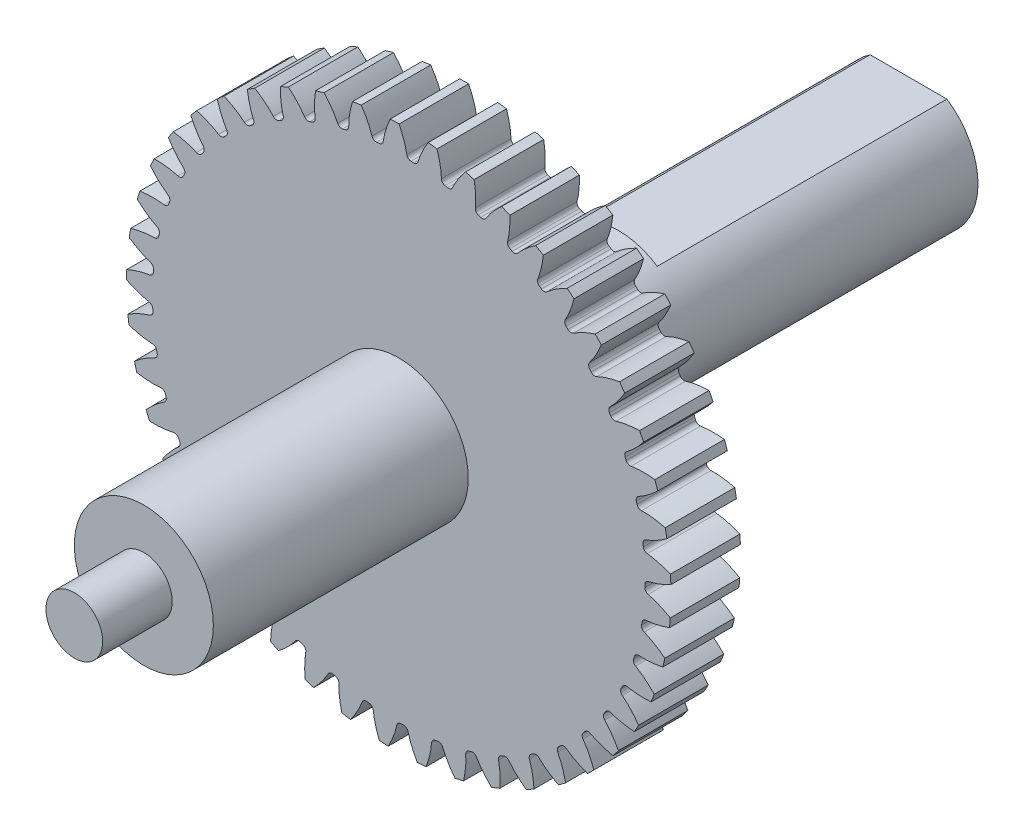
SolidWorks part; units mm, degrees
ref_plane "Front Plane" through (0, 0, 0) normal (0, 0, 1) x (1, 0, 0)
ref_plane "Top Plane" through (0, 0, 0) normal (0, 1, 0) x (1, 0, 0)
ref_plane "Right Plane" through (0, 0, 0) normal (1, 0, 0) x (0, 0, -1)
sketch "Sketch1" plane through (0, 0, 0) normal (0, 0, 1) x (1, 0, 0)
  circle A0 centre (0, 0) radius 3
  circle A1 centre (0, 0) radius 1.225
  dimension "D1" = 2.45
  dimension "D2" = 6
extrude "Boss-Extrude1" add sketch "Sketch1" along normal blind 33 contours A0
extrude "Boss-Extrude2" add sketch "Sketch1<3>" along normal blind 36 contours A1
sketch "Sketch1<3>" plane through (0, 0, 0) normal (0, 0, 1) x (1, 0, 0) same geometry as "Sketch1"
sketch "Sketch3" plane through (0, 0, 0) normal (0, 0, -1) x (-1, 0, 0)
  line L0 (-1.6583, 2.5) -> (1.6583, 2.5)
  line L1 (3.3, 0) -> (-3.3, 0) construction
  circle A0 centre (0, 0) radius 3 construction
  arc A1 (1.6583, 2.5) -> (-1.6583, 2.5) centre (0, 0) ccw
  dimension "D1" = 2.5
extrude "Cut-Extrude1" cut sketch "Sketch3" against normal blind 12.5
ref_plane "Plane1" through (0, 0, 19) normal (0, 0, 1) x (1, 0, 0)
sketch "Sketch4" plane through (0, 0, 19) normal (0, 0, 1) x (1, 0, 0)
  spline S0 degree 4 poles (10.5715, 0) (10.5764, 0.0001) (10.5899, 0.0006) (10.6154, 0.0024) (10.657, 0.0069) (10.7098, 0.0146) (10.7777, 0.0269) (10.8574, 0.0443) (10.9445, 0.0666) (11.0386, 0.0942) (11.1319, 0.1247) (11.2243, 0.1579) (11.3158, 0.1934) (11.4258, 0.2392) (11.5566, 0.2981) (11.7078, 0.3727) (11.8769, 0.4641) (12.0467, 0.5643) (12.2115, 0.6686) (12.3753, 0.7806) (12.5318, 0.8935) (12.6912, 1.0173) (12.8368, 1.135) (12.9963, 1.2738) (13.1239, 1.3879) (13.2882, 1.5458) (13.3839, 1.6413) (13.4945, 1.7555) (13.5428, 1.8075) (13.5726, 1.8395) knots 0 0 0 0 0 0.005377 0.015084 0.028532 0.04661 0.064855 0.092111 0.119476 0.146842 0.174209 0.201575 0.228941 0.256307 0.307035 0.361767 0.4165 0.471232 0.525964 0.580697 0.635429 0.690161 0.744894 0.799626 0.854358 0.909091 0.954545 1 1 1 1 1 construction
  spline S1 degree 4 poles (10.5715, 0) (10.5764, 0.0001) (10.5899, 0.0006) (10.6154, 0.0024) (10.657, 0.0069) (10.7098, 0.0146) (10.7777, 0.0269) (10.8574, 0.0443) (10.9445, 0.0666) (11.0386, 0.0942) (11.1319, 0.1247) (11.2243, 0.1579) (11.3158, 0.1934) (11.4258, 0.2392) (11.5566, 0.2981) (11.7078, 0.3727) (11.8769, 0.4641) (12.0467, 0.5643) (12.2115, 0.6686) (12.3753, 0.7806) (12.5318, 0.8935) (12.6912, 1.0173) (12.8368, 1.135) (12.9963, 1.2738) (13.1239, 1.3879) (13.2525, 1.5116) (13.3147, 1.5726) (13.3462, 1.6042) knots 0 0 0 0 0 0.005377 0.015084 0.028532 0.04661 0.064855 0.092111 0.119476 0.146842 0.174209 0.201575 0.228941 0.256307 0.307035 0.361767 0.4165 0.471232 0.525964 0.580697 0.635429 0.690161 0.744894 0.799626 0.854358 0.909091 0.909091 0.909091 0.909091 0.909091
sketch "Sketch5" plane through (0, 0, 19) normal (0, 0, 1) x (1, 0, 0)
  line L0 (0.1392, 0) -> (50000.1392, 0) construction
  line L2 (0, -0.1197) -> (0, -50000.1197) construction
  line L4 (0.8467, 0.0422) -> (49938.8312, 2489.5619) construction
  circle A0 centre (0, 0) radius 11.25 construction
  circle A1 centre (0, 0) radius 11.75
  circle A2 centre (0, 0) radius 10.5715 construction
  circle A3 centre (0, 0) radius 10.625
  arc A4 (10.7765, 0.0272) -> (10.6239, -0.1563) centre (10.8138, -0.1591) ccw
  arc A5 (10.7258, 1.0447) -> (10.5556, 1.2121) centre (10.7444, 1.2338) cw
  spline S0 degree 4 poles (-38.5192, 3999.3955) (8.4702, 38.101) (9.1923, 0.4865) (9.9476, -0.069) (10.657, 0.0069) (10.7098, 0.0146) (10.7777, 0.0269) (10.8574, 0.0443) (10.9445, 0.0666) (11.0386, 0.0942) (11.1319, 0.1247) (11.2243, 0.1579) (11.3158, 0.1934) (11.4258, 0.2392) (11.5566, 0.2981) (11.7078, 0.3727) (11.8769, 0.4641) (12.0467, 0.5643) (12.2115, 0.6686) (12.3753, 0.7806) (12.5318, 0.8935) (12.6912, 1.0173) (12.8368, 1.135) (12.9963, 1.2738) (13.8218, 2.012) (16.8775, 5.3381) (-43.1546, -54.2285) (2840.9669, 2830.5949) knots -0.748991 -0.748991 -0.748991 -0.748991 -0.748991 0.005377 0.015084 0.028532 0.04661 0.064855 0.092111 0.119476 0.146842 0.174209 0.201575 0.228941 0.256307 0.307035 0.361767 0.4165 0.471232 0.525964 0.580697 0.635429 0.690161 0.744894 0.799626 0.854358 2.106123 2.106123 2.106123 2.106123 2.106123 only from (10.5715, 0) to (13.3462, 1.6042) construction
  spline S1 degree 4 poles (10.7258, 1.0447) (10.7565, 1.0417) (10.8115, 1.0352) (10.8905, 1.0234) (10.9932, 1.0041) (11.0891, 0.983) (11.1844, 0.9592) (11.2789, 0.933) (11.393, 0.8984) (11.5164, 0.857) (11.6157, 0.8201) (11.6912, 0.7903) (11.7243, 0.7769) knots 0.057705 0.057705 0.057705 0.057705 0.057705 0.092111 0.119476 0.146842 0.174209 0.201575 0.228941 0.256307 0.307035 0.346885 0.346885 0.346885 0.346885 0.346885
  spline S2 degree 4 poles (10.7765, 0.0272) (10.8067, 0.0333) (10.8608, 0.0452) (10.9383, 0.0648) (11.0386, 0.0942) (11.1319, 0.1247) (11.2243, 0.1579) (11.3158, 0.1934) (11.4258, 0.2392) (11.5445, 0.2927) (11.6397, 0.3392) (11.7118, 0.3764) (11.7434, 0.393) knots 0.057705 0.057705 0.057705 0.057705 0.057705 0.092111 0.119476 0.146842 0.174209 0.201575 0.228941 0.256307 0.307035 0.346885 0.346885 0.346885 0.346885 0.346885
  point P6 (11.236, 0.5601)
  point P13 (11.2488, 0.1677)
  dimension "D1" = 22.5
  dimension "D2" = 21.1431
  dimension "D3" = 23.5
  dimension "D4" = 21.25
  dimension "D6" = 0.19
  dimension "D5" = 0.3927
extrude "Boss-Extrude3" add sketch "Sketch5" along normal blind 3 contours A3
extrude "Boss-Extrude5" add sketch "Sketch5<3>" along normal blind 3 contours A4 S2 A1 S1 A5 A3 region at (11.0851, 0.5526, 19)
sketch "Sketch5<3>" plane through (0, 0, 19) normal (0, 0, 1) x (1, 0, 0) same geometry as "Sketch5"
pattern_circular "CirPattern1" count 45 over 360 about axis through (0, 0, 22) along (0, 0, -1) of "Boss-Extrude5"
sketch "Sketch6" plane through (0, 0, 22) normal (0, 0, 1) x (1, 0, 0)
  circle A0 centre (0, 0) radius 11.25 construction
  circle A1 centre (0, 0) radius 11.25 construction
equation "\"m\"= 22.5 / 45mm'module"
equation "\"N\"= 45'number of teeth"
equation "\"a\"= 20deg'pressure angle"
equation "\"da\"= \"m\" * ( \"N\" + 2 )'addendum circle diameter"
equation "\"df\"= \"m\" * ( \"N\" - 2.5 )'dedendum circle diameter"
equation "\"db\"= \"m\" * \"N\" * cos ( \"a\" )'basic circle diameter"
equation "\"rb\"= \"db\" / 2'basic circle radius"
equation "\"s\"= \"m\" * pi / 2'pitch circle tooth thickness"
equation "\"r\"= \"m\" * 0.38'dedendum circle angle"
equation "\"B\"= \"d\" * 0.3'tooth width"
equation "\"d\"= 22.5mm"
equation "\"D1@Sketch5\"=\"d\""
equation "\"D2@Sketch5\"=\"db\""
equation "\"D3@Sketch5\"=\"da\""
equation "\"D4@Sketch5\"=\"df\""
equation "\"D5@Sketch5\"=\"s\"/2"
equation "\"D6@Sketch5\"=\"r\""
